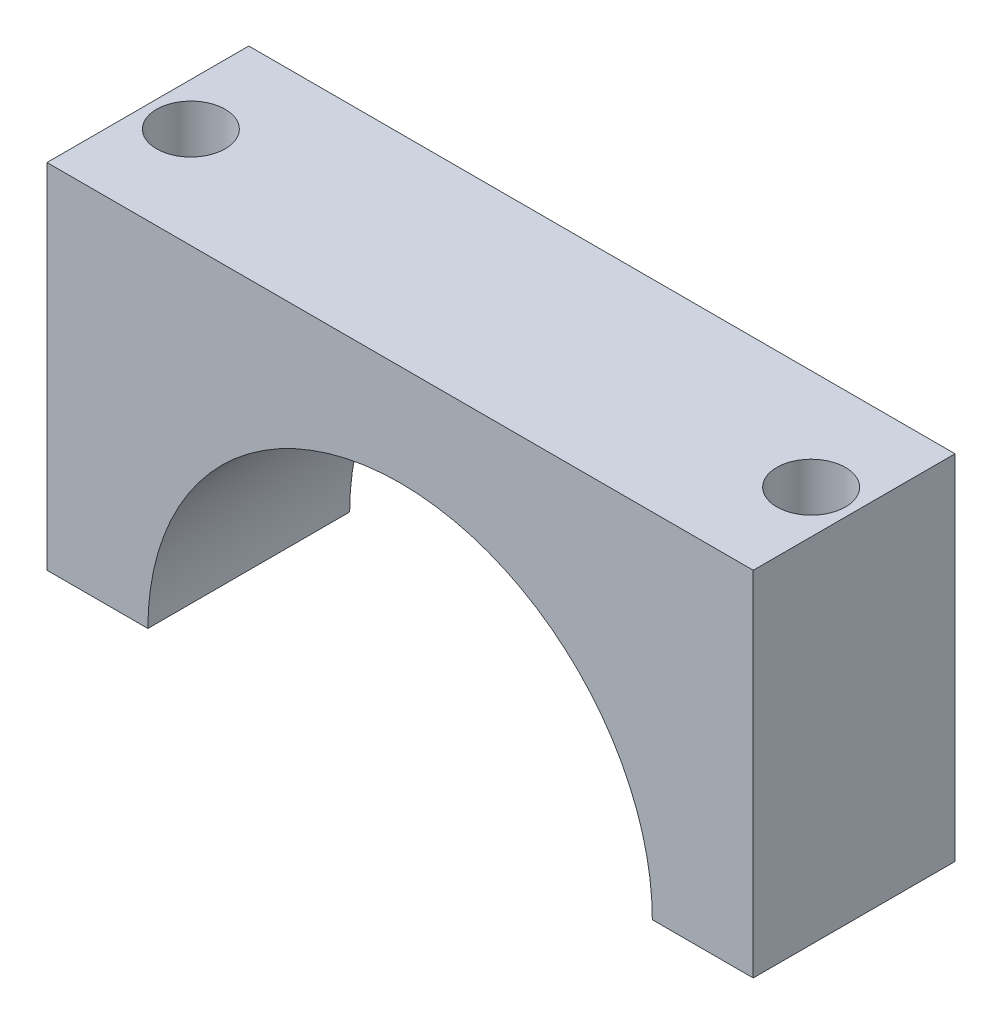
SolidWorks part; units mm, degrees
material "6061 Alloy"
ref_plane "Front Plane" through (0, 0, 0) normal (0, 0, 1) x (1, 0, 0)
ref_plane "Top Plane" through (0, 0, 0) normal (0, 1, 0) x (1, 0, 0)
ref_plane "Right Plane" through (0, 0, 0) normal (1, 0, 0) x (0, 0, -1)
sketch "Sketch2" plane through (0, 0, 0) normal (0, 0, 1) x (1, 0, 0)
  line L0 (12.5, 0) -> (17.5, 0)
  line L2 (-17.5, 0) -> (-17.5, 17.5)
  line L3 (-17.5, 17.5) -> (17.5, 17.5)
  line L4 (17.5, 0) -> (17.5, 17.5)
  line L7 (-12.5, 0) -> (-17.5, 0)
  arc A0 (12.5, 0) -> (-12.5, 0) centre (0, 0) ccw
  dimension "D1" = 12.5
  dimension "D2" = 17.5
  dimension "D3" = 35
  dimension "D4" = 17.5
extrude "Boss-Extrude1" add sketch "Sketch2" along normal blind 10
hole_wizard "M3 Clearance Hole1" positions "Sketch5" profile "Sketch4" hole size "M3" standard "ANSI Metric" end condition through all
sketch "Sketch5" plane through (0, 17.5, 0) normal (0, 1, 0) x (1, 0, 0)
  line L1 (17.5, -10) -> (-17.5, -10) construction
  line L7 (0, 0) -> (0, -10) construction
  line L8 (17.5, 0) -> (-17.5, 0) construction
  point P0 (-15.37, -5)
  point P2 (15.37, -5)
  dimension "D1" = 15.37
  dimension "D2" = 5
  dimension "D3" = 5
  dimension "D4" = 30.74
sketch "Sketch4" plane through (-15.37, 17.5, 5) normal (1, 0, 0) x (0, 0, 1)
  line L0 (0, 0) -> (0, 17.5)
  line L1 (0, 17.5) -> (1.7, 17.5)
  line L2 (1.7, 17.5) -> (1.7, 0)
  line L5 (1.7, 0) -> (0, 0)
  line L11 (0, -6.35) -> (0, 107.95) construction
  dimension "Thru Hole Dia." = 3.4
  dimension "Thru Hole Depth" = 17.5
